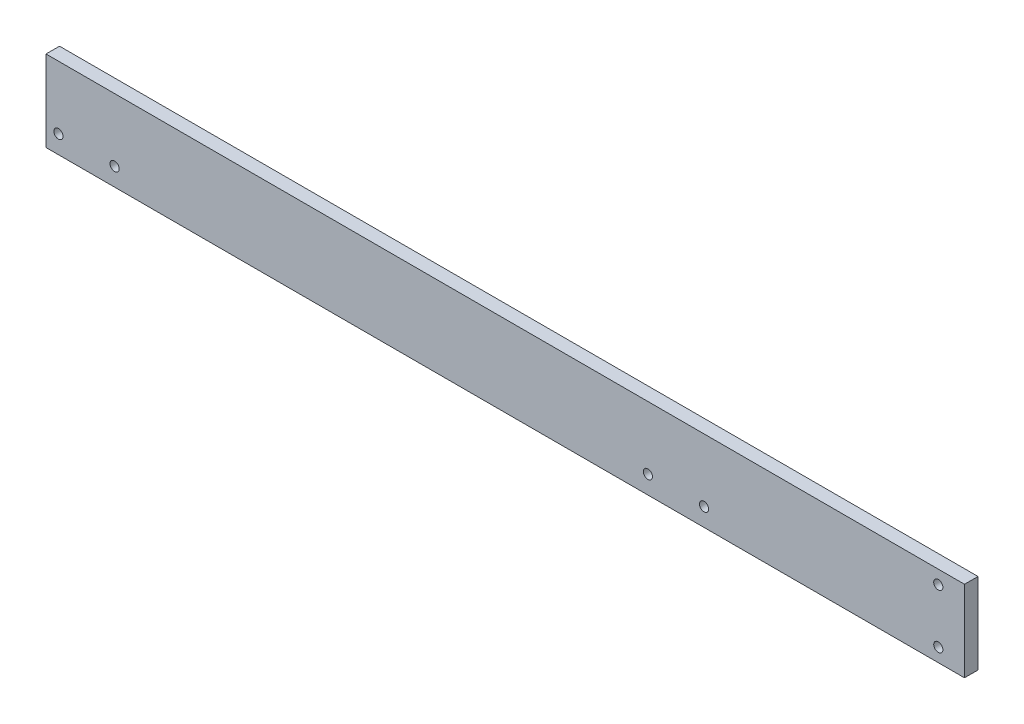
SolidWorks part; units mm, degrees
ref_plane "Front Plane" through (0, 0, 0) normal (0, 0, 1) x (1, 0, 0)
ref_plane "Top Plane" through (0, 0, 0) normal (0, 1, 0) x (1, 0, 0)
ref_plane "Right Plane" through (0, 0, 0) normal (1, 0, 0) x (0, 0, -1)
sketch "Sketch1" plane through (0, 0, 0) normal (0, 0, 1) x (1, 0, 0)
  line L1 (0, 0) -> (431.8, 0)
  line L2 (0, 0) -> (0, 38.1)
  line L3 (0, 38.1) -> (431.8, 38.1)
  line L4 (431.8, 0) -> (431.8, 38.1)
  dimension "D1" = 38.1
  dimension "D2" = 431.8
extrude "Boss-Extrude1" add sketch "Sketch1" along normal blind 6.35
sketch "Sketch3" plane through (0, 0, 6.35) normal (0, 0, 1) x (1, 0, 0)
  line L0 (9.525, 28.575) -> (204.3139, 9.525) construction
  line L1 (9.834, 31.7349) -> (204.623, 12.6849)
  line L2 (9.216, 25.4151) -> (204.0049, 6.3651)
  line L3 (9.525, 9.525) -> (204.3139, 28.575) construction
  line L4 (211.328, 38.1) -> (211.328, 0) construction
  line L7 (218.3421, 38.1) -> (218.3421, 0)
  line L8 (9.525, 28.575) -> (9.525, 9.525)
  line L9 (9.525, 9.525) -> (422.275, 9.525)
  line L10 (422.275, 9.525) -> (422.275, 28.575)
  line L11 (422.275, 28.575) -> (9.525, 28.575)
  line L12 (9.525, 28.575) -> (9.525, 9.525)
  line L13 (9.525, 9.525) -> (422.275, 9.525)
  line L15 (422.275, 28.575) -> (9.525, 28.575)
  line L16 (204.3139, 38.1) -> (204.3139, 0)
  line L17 (9.216, 12.6849) -> (204.0049, 31.7349)
  line L18 (9.834, 6.3651) -> (204.623, 25.4151)
  line L19 (215.9, 38.1) -> (215.9, 0) construction
  line L20 (211.328, 70.4248) -> (211.328, 0) construction
  line L21 (413.131, 9.525) -> (218.3421, 28.575) construction
  line L22 (413.44, 12.6849) -> (218.6511, 31.7349)
  line L23 (412.822, 6.3651) -> (218.033, 25.4151)
  line L24 (413.131, 28.575) -> (218.3421, 9.525) construction
  line L25 (412.822, 31.7349) -> (218.033, 12.6849)
  line L26 (413.44, 25.4151) -> (218.6511, 6.3651)
  line L27 (413.131, 37.592) -> (413.131, -0.508) construction
  line L28 (413.131, 37.592) -> (413.131, -0.508)
  arc A0 (218.3421, 38.1) -> (204.3139, 38.1) centre (211.328, 38.1) ccw
  arc A1 (204.3139, 0) -> (218.3421, 0) centre (211.328, 0) ccw
  arc A2 (9.834, 31.7349) -> (9.216, 25.4151) centre (9.525, 28.575) ccw
  arc A3 (204.0049, 6.3651) -> (204.623, 12.6849) centre (204.3139, 9.525) ccw
  arc A4 (9.216, 12.6849) -> (9.834, 6.3651) centre (9.525, 9.525) ccw
  arc A5 (204.623, 25.4151) -> (204.0049, 31.7349) centre (204.3139, 28.575) ccw
  arc A6 (413.44, 12.6849) -> (412.822, 6.3651) centre (413.131, 9.525) cw
  arc A7 (218.033, 25.4151) -> (218.6511, 31.7349) centre (218.3421, 28.575) cw
  arc A8 (412.822, 31.7349) -> (413.44, 25.4151) centre (413.131, 28.575) cw
  arc A9 (218.6511, 6.3651) -> (218.033, 12.6849) centre (218.3421, 9.525) cw
  point P7 (211.328, 19.05)
  point P16 (106.9195, 19.05)
  point P22 (106.9195, 19.05)
  point P33 (315.7365, 19.05)
  point P40 (315.7365, 19.05)
  dimension "D2" = 7.0141
  dimension "D3" = 3.175
  dimension "D1" = 9.525
extrude "Cut-Extrude1" [suppressed] cut sketch "Sketch3" against normal through all contours L12 L17 L2 | L1 L17 L15 | L18 L13 L2 | L18 L1 L16 | L25 L23 L7 | L25 L15 L22 | L23 L26 L13 | L28 L26 L22
fillet "Fillet1" [suppressed] radius 1.5875
sketch "Sketch4" plane through (0, 0, 0) normal (0, 0, -1) x (-1, 0, 0)
  line L0 (0, 19.05) -> (-395.8, 19.05) construction
  line L1 (0, 38.1) -> (0, 0) construction
  line L2 (-282.956, 8.509) -> (-309.372, 8.509) construction
  line L3 (-32.258, 8.509) -> (-5.842, 8.509) construction
  line L4 (-32.258, 8.509) -> (-282.956, 8.509) construction
  circle A0 centre (-419.481, 31.75) radius 2.1526
  circle A2 centre (-419.481, 6.35) radius 2.1526
  circle A3 centre (-309.372, 8.509) radius 2.1526
  circle A4 centre (-282.956, 8.509) radius 2.1526
  circle A5 centre (-32.258, 8.509) radius 2.1527
  circle A6 centre (-5.842, 8.509) radius 2.1526
  point P3 (0, 0)
  dimension "D4" = 4.3053
  dimension "D5" = 26.416
  dimension "D6" = 250.698
extrude "Cut-Extrude2" cut sketch "Sketch4" against normal through all
move or copy body "Body-Move/Copy1" [suppressed] bodies to move or copy 101 parameters "D1"=0, "D2"=0, "D3"=0
